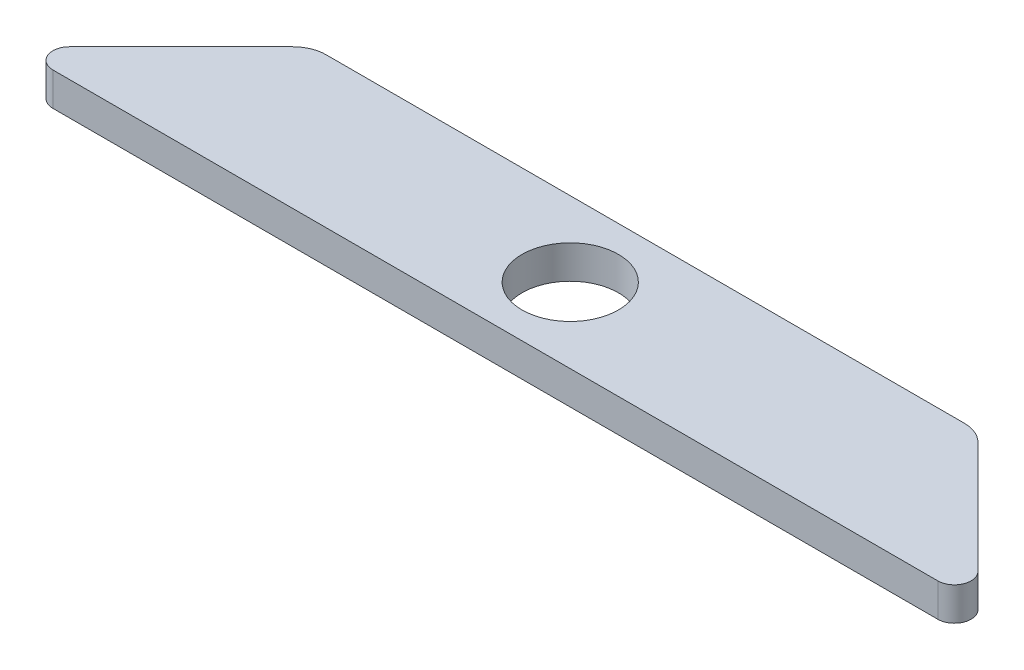
SolidWorks part; units mm, degrees
material "NEOPRENE"
ref_plane "Front Plane" through (0, 0, 0) normal (0, 0, 1) x (1, 0, 0)
ref_plane "Top Plane" through (0, 0, 0) normal (0, 1, 0) x (1, 0, 0)
ref_plane "Right Plane" through (0, 0, 0) normal (1, 0, 0) x (0, 0, -1)
sketch "Sketch1" plane through (0, 0, 0) normal (0, 1, 0) x (1, 0, 0)
  line L0 (-13.2929, -2.5303) -> (13.2929, -2.5303)
  line L1 (13.6464, -1.6768) -> (10.2929, 1.6768)
  line L2 (9.5858, 1.9697) -> (-9.5858, 1.9697)
  line L3 (-10.2929, 1.6768) -> (-13.6464, -1.6768)
  arc A0 (10.2929, 1.6768) -> (9.5858, 1.9697) centre (9.5858, 0.9697) ccw
  arc A1 (-9.5858, 1.9697) -> (-10.2929, 1.6768) centre (-9.5858, 0.9697) ccw
  arc A2 (13.2929, -2.5303) -> (13.6464, -1.6768) centre (13.2929, -2.0303) ccw
  arc A3 (-13.2929, -2.5303) -> (-13.6464, -1.6768) centre (-13.2929, -2.0303) cw
  point P2 (0, 1.9697)
  point P5 (-11.9697, 0)
  point P9 (10, 1.9697)
  point P12 (-10, 1.9697)
  dimension "D4" = 1
  dimension "D5" = 0.5
  dimension "D1" = 45
  dimension "D2" = 20
  dimension "D3" = 4.5
extrude "Boss-Extrude1" add sketch "Sketch1" along normal mid plane 1
sketch "Sketch2" plane through (0, 0.5, 0) normal (0, 1, 0) x (1, 0, 0)
  line L0 (9.5858, 1.9697) -> (-9.5858, 1.9697) construction
  circle A0 centre (0, -0.2803) radius 1.4478
  point P4 (0, 0)
  dimension "D1" = 2.25
  dimension "D2" = 2.8956
extrude "Cut-Extrude1" cut sketch "Sketch2" against normal up to next
